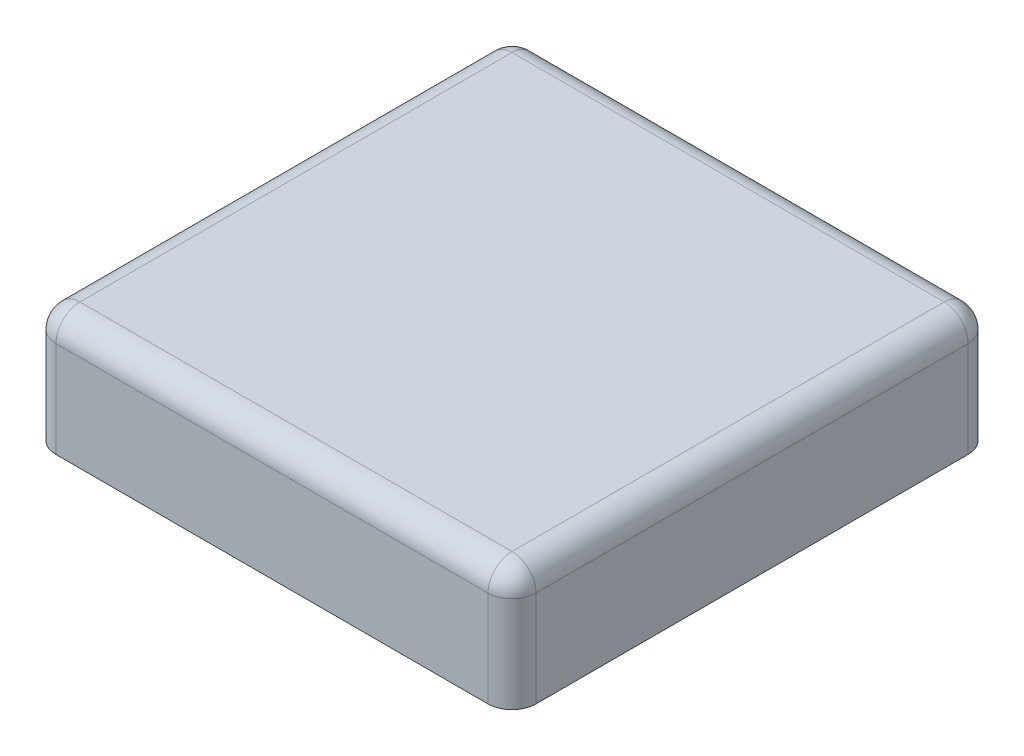
SolidWorks part; units mm, degrees
ref_plane "Front Plane" through (0, 0, 0) normal (0, 0, 1) x (1, 0, 0)
ref_plane "Top Plane" through (0, 0, 0) normal (0, 1, 0) x (1, 0, 0)
ref_plane "Right Plane" through (0, 0, 0) normal (1, 0, 0) x (0, 0, -1)
sketch "Sketch1" plane through (0, 0, 0) normal (0, 1, 0) x (1, 0, 0)
  line L1 (-30, 30) -> (30, 30)
  line L2 (-30, 30) -> (-30, -30)
  line L3 (-30, -30) -> (30, -30)
  line L4 (30, 30) -> (30, -30)
  line L5 (-30, 30) -> (30, -30) construction
  line L6 (-30, -30) -> (30, 30) construction
  point P0 (0, 0)
  dimension "D1" = 60
  dimension "D2" = 60
extrude "Boss-Extrude1" add sketch "Sketch1" along normal blind 15
fillet "Fillet1" radius 3 8 edges at (0, 15, 30) (-30, 15, 0) (0, 15, -30) (30, 15, 0) (30, 7.5, -30) (30, 7.5, 30) (-30, 7.5, 30) (-30, 7.5, -30)
shell "Shell1" thickness 3 removed face at (0, 0, 0)
